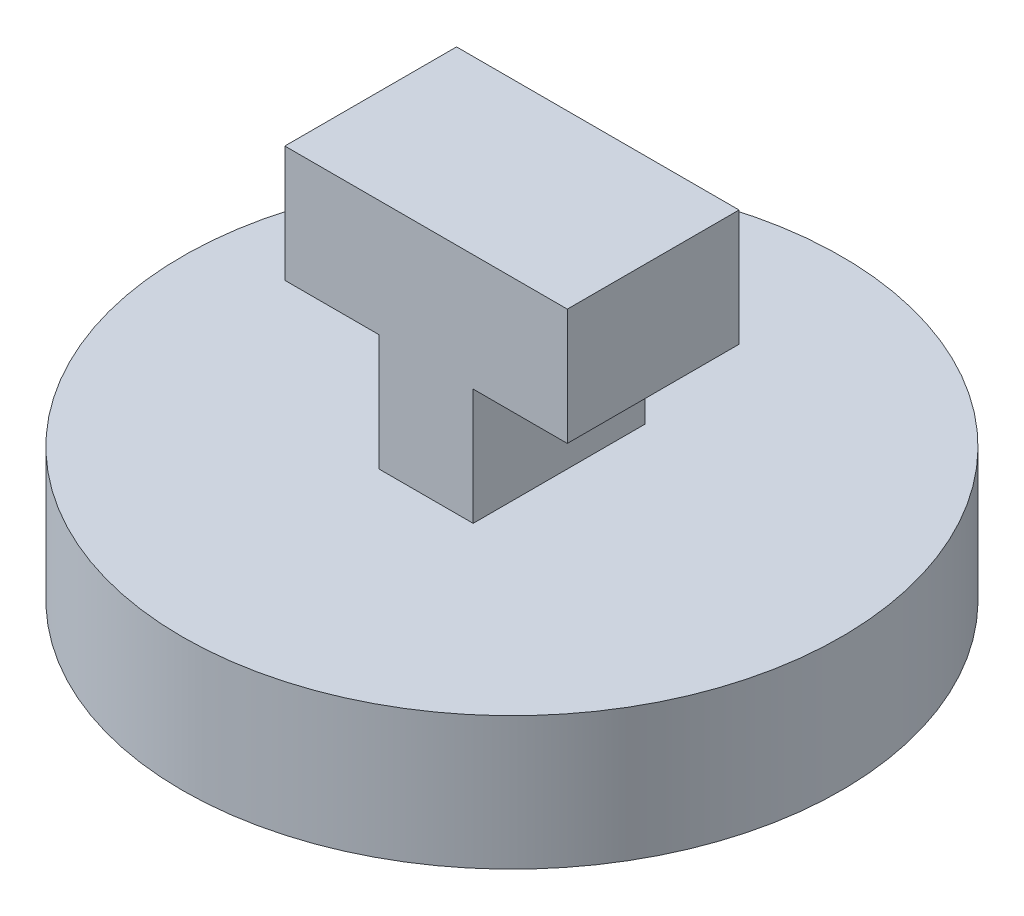
SolidWorks part; units mm, degrees
ref_plane "Front Plane" through (0, 0, 0) normal (0, 0, 1) x (1, 0, 0)
ref_plane "Top Plane" through (0, 0, 0) normal (0, 1, 0) x (1, 0, 0)
ref_plane "Right Plane" through (0, 0, 0) normal (1, 0, 0) x (0, 0, -1)
sketch "Sketch2" plane through (0, 0, 0) normal (0, 1, 0) x (1, 0, 0)
  circle A0 centre (0, 0) radius 5.95
  dimension "D1" = 11.9
extrude "Boss-Extrude2" add sketch "Sketch2" along normal blind 2.4
sketch "Sketch4" plane through (0, 0, 0) normal (0, 0, 1) x (1, 0, 0)
  line L0 (-0.85, 2.4) -> (-0.85, 4.5)
  line L1 (5.95, 2.4) -> (-5.95, 2.4) construction
  line L2 (-0.85, 4.5) -> (-2.55, 4.5)
  line L3 (-2.55, 4.5) -> (-2.55, 6.6)
  line L4 (-2.55, 6.6) -> (2.55, 6.6)
  line L5 (2.55, 6.6) -> (2.55, 4.5)
  line L6 (2.55, 4.5) -> (0.85, 4.5)
  line L7 (0.85, 4.5) -> (0.85, 2.4)
  line L8 (-0.85, 2.4) -> (0.85, 2.4)
  line L9 (0, 6.6) -> (0, 2.4) construction
  line L10 (5.95, 0) -> (5.95, 2.4) construction
  dimension "D1" = 2.1
  dimension "D2" = 2.1
  dimension "D3" = 5.1
  dimension "D4" = 1.7
  dimension "D5" = 1.7
  dimension "D6" = 5.95
extrude "Boss-Extrude3" add sketch "Sketch4" along normal blind 1.55 and the other way blind 1.55
